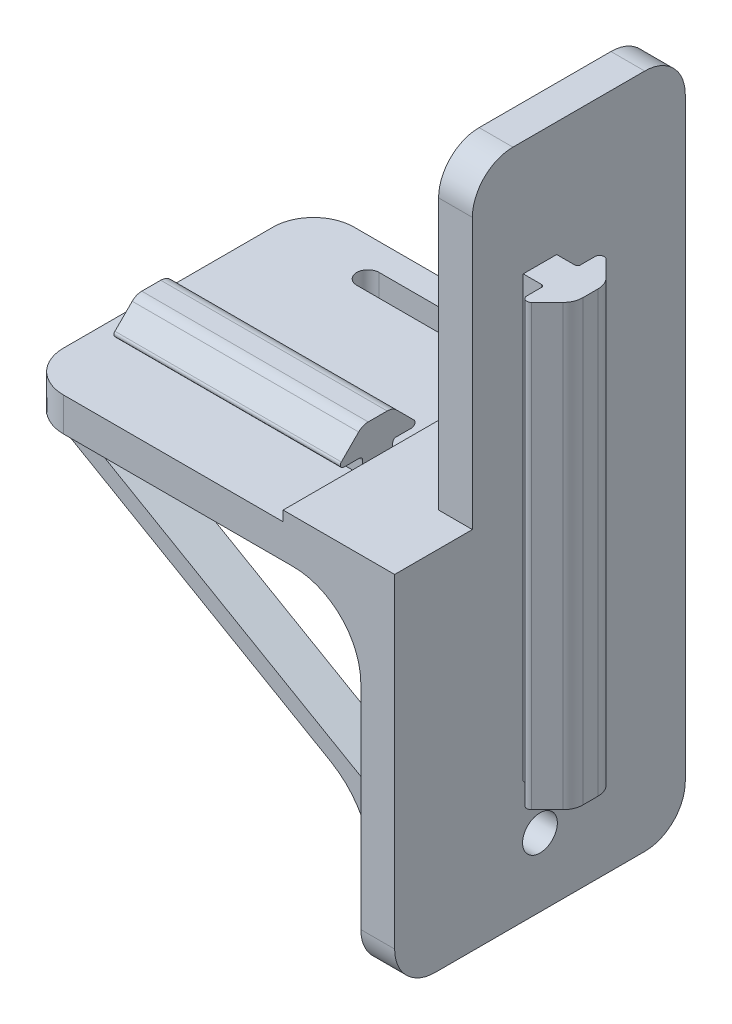
SolidWorks part; units mm, degrees
ref_plane "Front Plane" through (0, 0, 0) normal (0, 0, 1) x (1, 0, 0)
ref_plane "Top Plane" through (0, 0, 0) normal (0, 1, 0) x (1, 0, 0)
ref_plane "Right Plane" through (0, 0, 0) normal (1, 0, 0) x (0, 0, -1)
ref_plane "Plane3" through (0, 275, 0) normal (0, 1, 0) x (1, 0, 0)
sketch "Sketch1" plane through (0, 275, 0) normal (0, 1, 0) x (1, 0, 0)
  line L0 (389.6298, -111.5897) -> (387.1298, -111.5897)
  line L1 (389.6298, -106.6597) -> (387.1298, -106.6597)
  line L2 (387.1298, -106.6597) -> (387.1298, -111.5897)
  line L7 (390.3298, -111.6997) -> (389.6298, -111.6997) construction
  line L8 (389.6298, -106.5497) -> (390.3298, -106.5497) construction
  line L9 (390.6298, -114.1689) -> (390.6298, -111.9997) construction
  line L10 (394.3011, -112.3806) -> (391.9613, -114.7204) construction
  line L11 (395.1798, -107.9902) -> (395.1798, -110.2593) construction
  line L12 (390.6298, -106.2497) -> (390.6298, -104.0806) construction
  line L13 (391.9613, -103.5291) -> (394.3011, -105.8689) construction
  line L14 (389.6298, -106.6597) -> (390.3298, -106.6597)
  line L15 (390.7398, -106.2497) -> (390.7398, -104.0806)
  line L16 (391.8836, -103.6069) -> (394.2233, -105.9466)
  line L17 (395.0698, -107.9902) -> (395.0698, -110.2593)
  line L18 (394.2233, -112.3028) -> (391.8836, -114.6426)
  line L19 (390.7398, -114.1689) -> (390.7398, -111.9997)
  line L20 (390.3298, -111.5897) -> (389.6298, -111.5897)
  arc A6 (390.6298, -111.9997) -> (390.3298, -111.6997) centre (390.3298, -111.9997) ccw construction
  arc A7 (390.3298, -106.5497) -> (390.6298, -106.2497) centre (390.3298, -106.2497) ccw construction
  arc A8 (390.6298, -114.1689) -> (391.9613, -114.7204) centre (391.4098, -114.1689) ccw construction
  arc A9 (394.3011, -112.3806) -> (395.1798, -110.2593) centre (392.1798, -110.2593) ccw construction
  arc A10 (395.1798, -107.9902) -> (394.3011, -105.8689) centre (392.1798, -107.9902) ccw construction
  arc A11 (391.9613, -103.5291) -> (390.6298, -104.0806) centre (391.4098, -104.0806) ccw construction
  arc A12 (390.3298, -106.6597) -> (390.7398, -106.2497) centre (390.3298, -106.2497) ccw
  arc A13 (391.8836, -103.6069) -> (390.7398, -104.0806) centre (391.4098, -104.0806) ccw
  arc A14 (395.0698, -107.9902) -> (394.2233, -105.9466) centre (392.1798, -107.9902) ccw
  arc A15 (394.2233, -112.3028) -> (395.0698, -110.2593) centre (392.1798, -110.2593) ccw
  arc A16 (390.7398, -114.1689) -> (391.8836, -114.6426) centre (391.4098, -114.1689) ccw
  arc A17 (390.7398, -111.9997) -> (390.3298, -111.5897) centre (390.3298, -111.9997) ccw
  dimension "D2" = 2.5
  dimension "D1" = 0.11
ref_plane "Plane6" through (0, 245, 0) normal (0, 1, 0) x (1, 0, 0)
sketch "Sketch9" plane through (0, 245, 0) normal (0, 1, 0) x (1, 0, 0)
  line L0 (389.6298, -111.5997) -> (387.6298, -111.5997)
  line L1 (387.6298, -106.6497) -> (387.6298, -111.5997)
  line L7 (390.3298, -111.6897) -> (389.6298, -111.6897) construction
  line L8 (390.6298, -114.1589) -> (390.6298, -111.9897) construction
  line L9 (394.3011, -112.3706) -> (391.9613, -114.7104) construction
  line L10 (395.1798, -108.0002) -> (395.1798, -110.2493) construction
  line L11 (391.9613, -103.5391) -> (394.3011, -105.8789) construction
  line L12 (389.6298, -106.5597) -> (390.3298, -106.5597) construction
  line L13 (390.6298, -106.2597) -> (390.6298, -104.0906) construction
  line L14 (389.6298, -106.6497) -> (390.3298, -106.6497)
  line L15 (390.7198, -106.2597) -> (390.7198, -104.0906)
  line L16 (391.8977, -103.6027) -> (394.2375, -105.9425)
  line L17 (395.0898, -108.0002) -> (395.0898, -110.2493)
  line L18 (394.2375, -112.307) -> (391.8977, -114.6468)
  line L19 (390.7198, -114.1589) -> (390.7198, -111.9897)
  line L20 (390.3298, -111.5997) -> (389.6298, -111.5997)
  line L21 (389.6298, -106.6497) -> (387.6298, -106.6497)
  arc A6 (390.6298, -111.9897) -> (390.3298, -111.6897) centre (390.3298, -111.9897) ccw construction
  arc A7 (390.6298, -114.1589) -> (391.9613, -114.7104) centre (391.4098, -114.1589) ccw construction
  arc A8 (394.3011, -112.3706) -> (395.1798, -110.2493) centre (392.1798, -110.2493) ccw construction
  arc A9 (395.1798, -108.0002) -> (394.3011, -105.8789) centre (392.1798, -108.0002) ccw construction
  arc A10 (391.9613, -103.5391) -> (390.6298, -104.0906) centre (391.4098, -104.0906) ccw construction
  arc A11 (390.3298, -106.5597) -> (390.6298, -106.2597) centre (390.3298, -106.2597) ccw construction
  arc A12 (390.3298, -106.6497) -> (390.7198, -106.2597) centre (390.3298, -106.2597) ccw
  arc A13 (391.8977, -103.6027) -> (390.7198, -104.0906) centre (391.4098, -104.0906) ccw
  arc A14 (395.0898, -108.0002) -> (394.2375, -105.9425) centre (392.1798, -108.0002) ccw
  arc A15 (394.2375, -112.307) -> (395.0898, -110.2493) centre (392.1798, -110.2493) ccw
  arc A16 (390.7198, -114.1589) -> (391.8977, -114.6468) centre (391.4098, -114.1589) ccw
  arc A17 (390.7198, -111.9897) -> (390.3298, -111.5997) centre (390.3298, -111.9897) ccw
  dimension "D2" = 2
  dimension "D3" = 2
  dimension "D1" = 0.09
extrude "Boss-Extrude5" add sketch "Sketch9" against normal blind 50
ref_plane "Plane8" through (387.6298, 0, 0) normal (-1, 0, 0) x (0, 0, 1)
sketch "Sketch11" plane through (387.6298, 0, 0) normal (-1, 0, 0) x (0, 0, 1)
  line L1 (87.6247, 270) -> (130.6247, 270)
  line L2 (87.6247, 270) -> (87.6247, 170)
  line L3 (87.6247, 170) -> (130.6247, 170)
  line L4 (130.6247, 270) -> (130.6247, 170)
  line L5 (109.1247, 245) -> (109.1247, 188.6769) construction
  line L6 (106.6497, 245) -> (111.5997, 245) construction
  line L7 (106.6497, 220) -> (141.9101, 220) construction
  line L8 (106.6497, 195) -> (106.6497, 245) construction
  dimension "D1" = 21.5
  dimension "D2" = 21.5
  dimension "D3" = 50
  dimension "D4" = 50
extrude "Boss-Extrude6" add sketch "Sketch11" along normal blind 5
sketch "Sketch12" plane through (387.6298, 0, 0) normal (-1, 0, 0) x (0, 0, 1)
  line L0 (130.6247, 220) -> (87.6247, 220) construction
  line L1 (130.6247, 170) -> (130.6247, 270) construction
  line L2 (87.6247, 270) -> (87.6247, 170) construction
  line L3 (130.6247, 170) -> (130.6247, 270) construction
  line L4 (130.6247, 222.5) -> (89.1247, 222.5)
  line L5 (130.6247, 222.5) -> (130.6247, 217.5)
  line L6 (130.6247, 217.5) -> (89.1247, 217.5)
  line L7 (89.1247, 222.5) -> (87.6247, 222.5)
  line L8 (89.1247, 217.5) -> (87.6247, 217.5)
  line L9 (87.6247, 222.5) -> (87.6247, 217.5)
  dimension "D1" = 2.5
  dimension "D2" = 2.5
extrude "Boss-Extrude8" add sketch "Sketch12" along normal blind 55
sketch "Sketch13" plane through (387.6298, 0, 0) normal (-1, 0, 0) x (0, 0, 1)
  line L0 (119.1247, 8.5) -> (119.1247, 408.5) construction
  line L1 (119.1247, 222.5) -> (119.1247, 270)
  line L2 (87.6247, 222.5) -> (130.6247, 222.5) construction
  line L3 (119.1247, 222.5) -> (130.6247, 222.5)
  line L4 (130.6247, 222.5) -> (130.6247, 270) construction
  line L5 (130.6247, 270) -> (87.6247, 270) construction
  line L6 (130.6247, 222.5) -> (130.6247, 270)
  line L7 (130.6247, 270) -> (119.1247, 270)
extrude "Cut-Extrude1" cut sketch "Sketch13" along normal blind 55
ref_plane "Plane9" through (0, 0, 129.1247) normal (0, 0, 1) x (1, 0, 0)
sketch "Sketch15" plane through (0, 0, 129.1247) normal (0, 0, 1) x (1, 0, 0)
  line L0 (335.6298, 217.5) -> (382.6298, 190.3645)
  line L1 (332.6298, 217.5) -> (382.6298, 217.5) construction
  line L2 (382.6298, 170) -> (382.6298, 217.5) construction
  line L3 (332.6298, 217.5) -> (382.6298, 217.5) construction
  line L4 (335.6298, 217.5) -> (340.6298, 217.5)
  line L7 (382.6298, 190.3645) -> (382.6298, 193.2513)
  line L8 (340.6298, 217.5) -> (382.6298, 193.2513)
  point P6 (332.6298, 217.5)
  dimension "D1" = 3
  dimension "D2" = 30
  dimension "D3" = 5
  dimension "D4" = 30
ref_plane "Plane10" through (332.6298, 0, 0) normal (-1, 0, 0) x (0, 0, 1)
ref_plane "Plane11" through (382.6298, 0, 0) normal (-1, 0, 0) x (0, 0, 1)
extrude "Boss-Extrude9" add sketch "Sketch15" against normal blind 6
fillet "Fillet7" radius 12 2 edges at (335.6298, 217.5, 126.1247) (382.6298, 190.3645, 126.1247)
ref_plane "Plane12" through (0, 0, 110.6247) normal (0, 0, 1) x (1, 0, 0)
mirror "Mirror1" about plane through (0, 0, 110.6247) normal (0, 0, 1) of "Boss-Extrude9", "Fillet7"
fillet "Fillet8" radius 6 6 edges at (385.1298, 170, 87.6247) (385.1298, 170, 130.6247) (332.6298, 220, 130.6247) (385.1298, 270, 87.6247) (385.1298, 270, 119.1247) (332.6298, 220, 87.6247)
extrude "Boss-Extrude10" add sketch "Sketch9<2>" along normal blind 8
sketch "Sketch9<2>" plane through (0, 245, 0) normal (0, 1, 0) x (1, 0, 0) same geometry as "Sketch9"
fillet "Fillet12" radius 10 1 edges at (382.6298, 217.5, 109.1247)
extrude "Boss-Extrude11" add sketch "Sketch9<3>" against normal blind 57
sketch "Sketch9<3>" plane through (0, 245, 0) normal (0, 1, 0) x (1, 0, 0) same geometry as "Sketch9"
ref_plane "Plane13" through (382.6298, 0, 0) normal (-1, 0, 0) x (0, 0, 1)
sketch "Sketch16" plane through (382.6298, 0, 0) normal (-1, 0, 0) x (0, 0, 1)
  line L1 (111.6997, 8.5) -> (111.6997, 408.5) construction
  line L3 (111.6997, 8.5) -> (111.6997, 408.5) construction
  line L4 (111.6997, 8.5) -> (111.6997, 408.5) construction
  line L5 (111.6997, 8.5) -> (111.6997, 408.5) construction
  line L6 (106.5497, 8.5) -> (106.5497, 408.5) construction
  line L7 (106.5497, 8.5) -> (106.5497, 408.5) construction
  line L9 (109.1247, 162.2841) -> (109.1247, 197.982) construction
  circle A0 centre (109.1247, 180.1331) radius 2.575
  dimension "D2" = 5.15
extrude "Cut-Extrude2" cut sketch "Sketch16" against normal blind 10
sketch "Sketch17" plane through (371.1298, 0, 0) normal (1, 0, 0) x (0, 0, -1)
  line L2 (-103.1446, 222.5) -> (-103.1446, 224)
  line L3 (-130.6247, 222.5) -> (-103.1446, 222.5)
  line L4 (-130.6247, 224) -> (-130.6247, 222.5)
  line L5 (-130.6247, 224) -> (-103.1446, 224)
  dimension "D1" = 1.5
extrude "Boss-Extrude12" add sketch "Sketch17" along normal up to surface (11.5 mm away) up to face at (382.6298, 252.5809, 103.3747)
sketch "Sketch18" plane through (382.6298, 0, 0) normal (1, 0, 0) x (0, 0, -1)
  line L0 (-119.1247, 222.5) -> (-119.1247, 224) construction
  line L1 (-130.6247, 224) -> (-119.1247, 224) construction
  line L2 (-119.1247, 222.5) -> (-130.6247, 222.5) construction
  line L3 (-130.6247, 222.5) -> (-130.6247, 224) construction
  line L4 (-119.1247, 222.5) -> (-119.1247, 224)
  line L5 (-130.6247, 224) -> (-119.1247, 224)
  line L6 (-119.1247, 222.5) -> (-130.6247, 222.5)
  line L7 (-130.6247, 222.5) -> (-130.6247, 224)
extrude "Boss-Extrude13" add sketch "Sketch18" along normal up to surface (5 mm away) up to face at (387.6298, 177.5581, 109.1247)
sketch "Sketch19" plane through (332.6298, 0, 0) normal (-1, 0, 0) x (0, 0, 1)
  line L12 (125.1447, 227.49) -> (125.1447, 228.51)
  line L13 (122.6447, 227.49) -> (125.1447, 227.49)
  line L14 (122.6447, 227.0027) -> (122.6447, 227.49)
  line L15 (124.745, 223.3679) -> (122.6447, 227.0027)
  line L16 (124.745, 222.5) -> (124.745, 223.3679)
  line L17 (108.5243, 222.5) -> (124.745, 222.5)
  line L18 (108.5243, 223.3679) -> (108.5243, 222.5)
  line L19 (110.6247, 227.0027) -> (108.5243, 223.3679)
  line L20 (110.6247, 227.49) -> (110.6247, 227.0027)
  line L21 (108.1247, 227.49) -> (110.6247, 227.49)
  line L22 (108.1247, 228.51) -> (108.1247, 227.49)
  line L23 (125.1447, 228.51) -> (108.1247, 228.51)
extrude "Boss-Extrude14" [suppressed] add sketch "Sketch19" against normal up to surface (33.5 mm away) from offset 5 offset against normal yes
sketch "Sketch22" plane through (332.6298, 0, 0) normal (-1, 0, 0) x (0, 0, 1)
  line L9 (114.4062, 222.5) -> (114.4062, 224.5)
  line L10 (124.6247, 222.5) -> (93.6247, 222.5) construction
  line L11 (116.6347, 229) -> (116.6347, 219.5991) construction
  line L12 (118.8632, 222.5) -> (114.4062, 222.5)
  line L13 (113.9062, 225) -> (111.6133, 225)
  line L14 (111.2597, 225.8536) -> (113.8204, 228.4142)
  line L15 (115.2346, 229) -> (116.6347, 229)
  line L16 (118.8632, 222.5) -> (118.8632, 224.5)
  line L17 (119.3632, 225) -> (121.6561, 225)
  line L18 (118.0348, 229) -> (116.6347, 229)
  line L19 (122.0096, 225.8536) -> (119.449, 228.4142)
  arc A6 (115.2346, 229) -> (113.8204, 228.4142) centre (115.2346, 227) ccw
  arc A7 (111.6133, 225) -> (111.2597, 225.8536) centre (111.6133, 225.5) cw
  arc A8 (114.4062, 224.5) -> (113.9062, 225) centre (113.9062, 224.5) ccw
  arc A9 (118.8632, 224.5) -> (119.3632, 225) centre (119.3632, 224.5) cw
  arc A10 (121.6561, 225) -> (122.0096, 225.8536) centre (121.6561, 225.5) ccw
  arc A11 (118.0348, 229) -> (119.449, 228.4142) centre (118.0348, 227) cw
  point P36 (110.4062, 225)
  point P39 (114.4062, 225)
  point P40 (115.9346, 229)
  point P48 (117.3347, 229)
  dimension "D3" = 2
  dimension "D4" = 0.5
  dimension "D7" = 0.5
  dimension "D1" = 2.5
  dimension "D2" = 4
  dimension "D5" = 45
  dimension "D6" = 6.5
extrude "Boss-Extrude15" add sketch "Sketch22" against normal blind 33.5 from offset 5 offset against normal yes
sketch "Sketch23" plane through (0, 222.5, 0) normal (0, 1, 0) x (1, 0, 0)
  line L0 (346.2798, -93.2267) -> (374.9798, -93.2267) construction
  line L1 (337.6298, -98.8287) -> (371.1298, -98.8287) construction
  line L2 (338.6298, -87.6247) -> (382.6298, -87.6247) construction
  line L3 (338.6298, -98.8287) -> (371.1298, -98.8287) construction
  line L4 (338.6298, -87.6247) -> (371.1298, -87.6247) construction
  line L6 (338.6298, -93.2267) -> (382.6298, -93.2267) construction
  line L7 (338.6298, -87.6247) -> (338.6298, -98.8287) construction
  line L10 (382.6298, -113.1247) -> (382.6298, -93.6247) construction
  line L11 (382.6298, -87.6247) -> (382.6298, -93.6247) construction
  line L12 (382.6298, -113.1247) -> (382.6298, -93.6247) construction
  line L13 (382.6298, -87.6247) -> (382.6298, -93.6247) construction
  line L14 (346.2798, -91.5767) -> (374.9798, -91.5767)
  line L15 (346.2798, -94.8767) -> (374.9798, -94.8767)
  arc A2 (346.2798, -91.5767) -> (346.2798, -94.8767) centre (346.2798, -93.2267) ccw
  arc A3 (374.9798, -94.8767) -> (374.9798, -91.5767) centre (374.9798, -93.2267) ccw
  point P10 (360.6298, -93.2267)
  point P17 (376.6298, -93.2267)
  point P18 (344.6298, -93.2267)
  dimension "D1" = 6
  dimension "3.3" = 3.3
  dimension "D2" = 6
extrude "Cut-Extrude3" cut sketch "Sketch23" against normal blind 6
